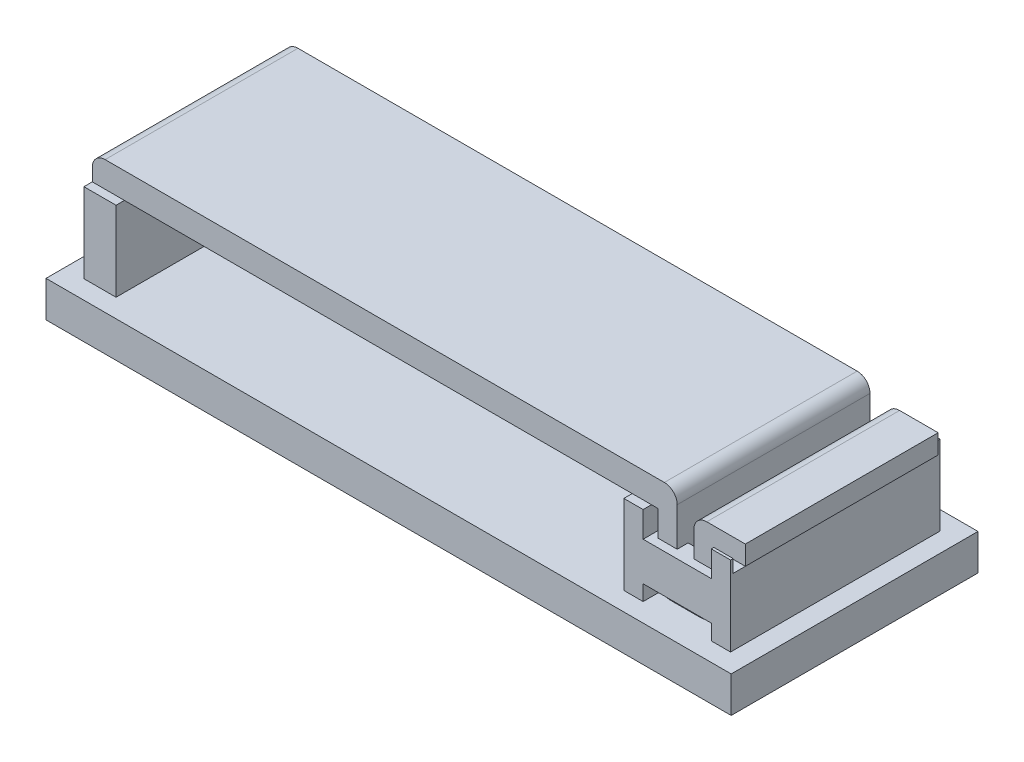
SolidWorks part; units mm, degrees
ref_plane "Front Plane" through (0, 0, 0) normal (0, 0, 1) x (1, 0, 0)
ref_plane "Top Plane" through (0, 0, 0) normal (0, 1, 0) x (1, 0, 0)
ref_plane "Right Plane" through (0, 0, 0) normal (1, 0, 0) x (0, 0, -1)
sketch "Base Outline" plane through (0, 0, 0) normal (0, 1, 0) x (1, 0, 0)
  line L1 (-26.65, -9.6) -> (26.65, -9.6)
  line L2 (-26.65, -9.6) -> (-26.65, 9.6)
  line L3 (-26.65, 9.6) -> (26.65, 9.6)
  line L4 (26.65, -9.6) -> (26.65, 9.6)
  point P4 (0, 9.6)
  point P6 (26.65, 0)
  dimension "Overall_Length" = 53.3
  dimension "Overall_Width" = 19.2
extrude "Clamp Base" add sketch "Base Outline" along normal blind 2.8
sketch "Hinge and Latch Outline" plane through (0, 0, 0) normal (0, 0, 1) x (1, 0, 0)
  line L0 (-26.65, 2.8) -> (26.65, 2.8) construction
  line L1 (-26.65, 2.8) -> (26.65, 2.8) construction
  line L2 (-25.15, 2.8) -> (-25.15, 9)
  line L3 (-25.15, 9) -> (-22.65, 9)
  line L4 (-22.65, 9) -> (-22.65, 2.8)
  line L5 (-25.15, 2.8) -> (-22.65, 2.8)
  line L6 (16.85, 2.8) -> (16.85, 9)
  line L7 (16.85, 2.8) -> (25.15, 2.8)
  line L9 (25.15, 2.8) -> (25.15, 9)
  line L10 (25.15, 9) -> (16.85, 9)
  point P2 (-25.15, 2.8)
  point P3 (25.15, 2.8)
  point P6 (-22.65, 2.8)
  point P10 (16.85, 2.8)
  dimension "Cable_Height" = 6.2
  dimension "Maximum_Cable_Width" = 39.5
extrude "Clip Hinge and Latch" add sketch "Hinge and Latch Outline" along normal mid plane 16.3
sketch "Side Cuts Outline" plane through (0, 0, 8.15) normal (0, 0, 1) x (1, 0, 0)
  line L0 (25.15, 9) -> (16.85, 9) construction
  line L1 (16.85, 2.8) -> (25.15, 2.8) construction
  line L3 (18.35, 9) -> (23.65, 9)
  line L4 (18.35, 9) -> (18.35, 7)
  line L5 (18.35, 7) -> (23.65, 7)
  line L6 (23.65, 9) -> (23.65, 7)
  line L7 (18.35, 2.8) -> (23.65, 2.8)
  line L8 (18.35, 2.8) -> (18.35, 4)
  line L9 (18.35, 4) -> (23.65, 4)
  line L10 (23.65, 2.8) -> (23.65, 4)
  point P0 (21, 9)
  point P1 (21, 2.8)
  point P14 (21, 7)
  point P15 (21, 4)
  dimension "Side_Cut_One_Depth" = 2
  dimension "Side_Cut_Two_Depth" = 1.2
  dimension "Side_Cut_Width" = 5.3
extrude "Latch Sides Cut" cut sketch "Side Cuts Outline" against normal up to next
sketch "Through Cut Outline" plane through (0, 7, 0) normal (0, 1, 0) x (1, 0, 0)
  line L2 (18.35, 8.15) -> (18.35, -8.15) construction
  line L3 (23.65, 8.15) -> (23.65, -8.15) construction
  line L5 (18.35, 6.65) -> (23.65, 6.65)
  line L6 (18.35, 6.65) -> (18.35, -6.65)
  line L7 (18.35, -6.65) -> (23.65, -6.65)
  line L8 (23.65, 6.65) -> (23.65, -6.65)
  point P0 (18.35, 6.65)
  point P1 (23.65, -6.65)
extrude "Latch Through Cut" cut sketch "Through Cut Outline" against normal up to next
sketch "Front Cut Outline" plane through (25.15, 0, 0) normal (1, 0, 0) x (0, 0, -1)
  line L1 (-8.15, 9) -> (8.15, 9) construction
  line L2 (-7.95, 9) -> (7.95, 9)
  line L3 (-7.95, 9) -> (-7.95, 8)
  line L4 (-7.95, 8) -> (7.95, 8)
  line L5 (7.95, 9) -> (7.95, 8)
  point P0 (0, 9)
  point P7 (0, 9)
  point P8 (0, 8)
  dimension "Front_Cut_Depth" = 1
  dimension "Front Cut Width" = 15.9
extrude "Latch Front Cut" cut sketch "Front Cut Outline" against normal up to next
sketch "Mid-Point Latch Back Point" plane through (0, 9, 0) normal (0, 1, 0) x (1, 0, 0)
  line L0 (18.35, 8.15) -> (18.35, -8.15) construction
  line L1 (18.35, 8.15) -> (18.35, -8.15) construction
  point P2 (18.35, 0)
sketch "Mid-Point Latch Front Point" plane through (0, 8, 0) normal (0, 1, 0) x (1, 0, 0)
  line L0 (23.65, 7.95) -> (23.65, -7.95) construction
  line L1 (23.65, 7.95) -> (23.65, -7.95) construction
  point P2 (23.65, 0)
sketch "Clamp Outline" plane through (0, 0, 0) normal (0, 0, 1) x (1, 0, 0)
  line L0 (-26.65, 2.8) -> (26.65, 2.8) construction
  line L1 (-25.15, 9) -> (18.85, 9)
  line L2 (-25.15, 9) -> (-25.15, 11)
  line L3 (-25.15, 11) -> (20.35, 11)
  line L4 (18.85, 9) -> (18.85, 3.3)
  line L5 (18.85, 3.3) -> (23.15, 3.3)
  line L6 (-26.65, 2.8) -> (26.65, 2.8) construction
  line L8 (20.35, 11) -> (20.35, 4.8)
  line L9 (21.65, 10) -> (25.65, 10)
  line L12 (21.65, 10) -> (21.65, 4.8)
  line L14 (23.15, 8.5) -> (23.15, 3.3)
  line L15 (25.65, 8.5) -> (25.65, 10)
  line L16 (20.35, 4.8) -> (21.65, 4.8)
  line L17 (25.65, 8.5) -> (23.15, 8.5)
  point P21 (25.65, 8.5)
  dimension "D1" = 0.5
  dimension "D2" = 0.5
  dimension "D3" = 0.5
  dimension "D7" = 0.5
  dimension "Finger_Pad_Width" = 4
  dimension "Clamp_Thickness" = 2
extrude "Clamp" add sketch "Clamp Outline" along normal mid plane 15
fillet "Clamp Fillets" radius 1 6 edges at (23.15, 8.5, 0) (21.65, 10, 0) (20.35, 11, 0) (-25.15, 11, 0) (23.15, 3.3, 0) (18.85, 3.3, 0)
sketch3d "Centre Lines Through Clips"
  line L0 (-22.65, 5.9, 8.15) -> (16.85, 5.9, 8.15) construction
  line L1 (16.85, 5.9, -8.15) -> (-22.65, 5.9, -8.15) construction
  line L4 (16.85, 9, 8.15) -> (16.85, 2.8, 8.15) construction
  line L5 (16.85, 9, -8.15) -> (16.85, 2.8, -8.15) construction
  line L7 (-22.65, 2.8, 8.15) -> (-22.65, 9, 8.15) construction
  line L8 (-2.9, 5.9, 8.15) -> (-2.9, 5.9, -8.15) construction
  line L9 (-22.65, 2.8, -8.15) -> (-22.65, 9, -8.15) construction
  line L10 (-22.65, 2.8, 8.15) -> (-22.65, 9, 8.15) construction
  line L11 (-22.65, 2.8, -8.15) -> (-22.65, 9, -8.15) construction
  point P2 (-3, 5.9, 8.45)
  point P5 (-2.9, 5.9, -8.15)
ref_axis "Ribbon Cable Axis" through (-2.9, 5.9, 8.15) along (0, 0, -1)
